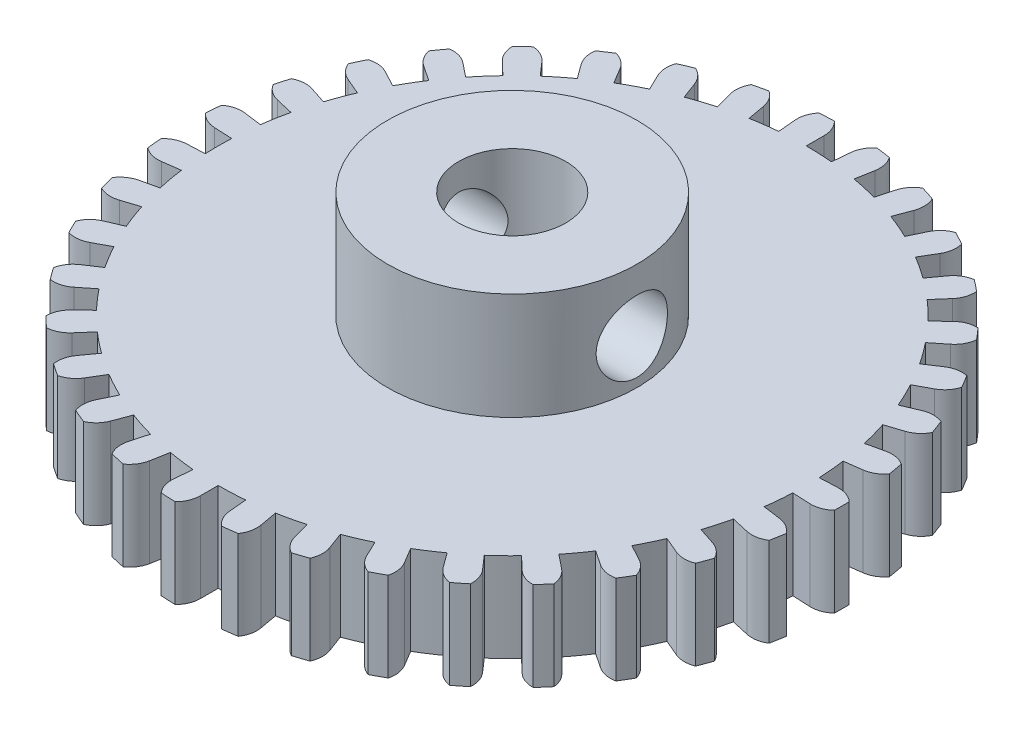
SolidWorks part; units mm, degrees
material "0.7060 (EN-GJS-600-3)"
ref_plane "Front" through (0, 0, 0) normal (0, 0, 1) x (1, 0, 0)
ref_plane "Top" through (0, 0, 0) normal (0, 1, 0) x (1, 0, 0)
ref_plane "Right" through (0, 0, 0) normal (1, 0, 0) x (0, 0, -1)
sketch "Sketch1" plane through (0, 0, 0) normal (0, 1, 0) x (1, 0, 0)
  line L0 (0, 0) -> (21.1577, 0) construction
  line L1 (0, 0) -> (16.4335, 1.4797) construction
  line L2 (0, 0) -> (23.2285, 1.0436) construction
  line L3 (0, 0) -> (18.0087, 0.4043) construction
  line L4 (16.4834, 0.7406) -> (17.4824, 0.7855)
  line L5 (0, 0) -> (16.4335, 1.4797)
  line L6 (16.4834, -0.7406) -> (17.4824, -0.7855)
  line L7 (0, 0) -> (16.4335, -1.4797)
  circle A0 centre (0, 0) radius 18.5 construction
  circle A1 centre (0, 0) radius 17.5 construction
  circle A2 centre (0, 0) radius 16.5 construction
  arc A3 (17.4824, 0.7855) -> (18.4953, 0.4153) centre (17.5452, -0.6136) cw
  arc A4 (16.4834, 0.7406) -> (16.4335, 1.4797) centre (0, 0) ccw
  arc A5 (18.4953, 0.4153) -> (18.4953, -0.4153) centre (0, 0) cw
  arc A6 (17.4824, -0.7855) -> (18.4953, -0.4153) centre (17.5452, 0.6136) ccw
  arc A7 (16.4834, -0.7406) -> (16.4335, -1.4797) centre (0, 0) cw
  point P19 (-133.6375, 17.955)
  dimension "D1" = 37
  dimension "D2" = 35
  dimension "D3" = 2
  dimension "D4" = 5.145
  dimension "D5" = 2.573
  dimension "D6" = 1.286
extrude "Boss-Extrude1" add sketch "Sketch1" along normal blind 5
pattern_circular "CirPattern1" count 35 over 360 about axis through (0, 5, 0) along (0, -1, 0) of "Boss-Extrude1" reverse direction yes
sketch "Sketch2" plane through (0, 5, 0) normal (0, 1, 0) x (1, 0, 0)
  circle A0 centre (0, 0) radius 7
  circle A1 centre (0, 0) radius 3
  dimension "D1" = 6
  dimension "D2" = 14
extrude "Cut-Extrude1" cut sketch "Sketch2" against normal through all both and the other way through all contours A1
extrude "Boss-Extrude2" add sketch "Sketch2<3>" along normal blind 6
sketch "Sketch2<3>" plane through (0, 5, 0) normal (0, 1, 0) x (1, 0, 0) same geometry as "Sketch2"
sketch "Sketch3" plane through (0, 0, 0) normal (1, 0, 0) x (0, 0, -1)
  circle A0 centre (0, 7.5) radius 2
  point P2 (0, 0)
  dimension "D1" = 4
  dimension "D2" = 7.5
extrude "Cut-Extrude2" cut sketch "Sketch3" against normal through all both and the other way through all
